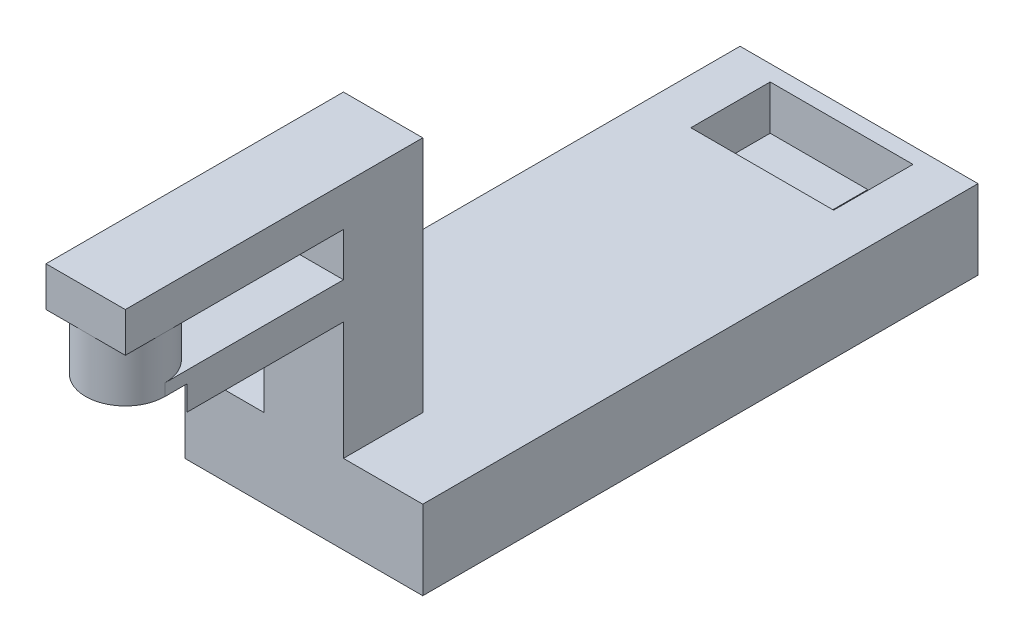
SolidWorks part; units mm, degrees
ref_plane "Front Plane" through (0, 0, 0) normal (0, 0, 1) x (1, 0, 0)
ref_plane "Top Plane" through (0, 0, 0) normal (0, 1, 0) x (1, 0, 0)
ref_plane "Right Plane" through (0, 0, 0) normal (1, 0, 0) x (0, 0, -1)
sketch "Sketch1" plane through (0, 0, 0) normal (0, 0, 1) x (1, 0, 0)
  line L1 (-6.35, -25.4) -> (6.35, -25.4)
  line L2 (-6.35, -25.4) -> (-6.35, 25.4)
  line L3 (-6.35, 25.4) -> (6.35, 25.4)
  line L4 (6.35, -25.4) -> (6.35, 25.4)
  line L5 (-6.35, -25.4) -> (6.35, 25.4) construction
  line L6 (-6.35, 25.4) -> (6.35, -25.4) construction
  point P0 (0, 0)
  dimension "D1" = 12.7
  dimension "D2" = 50.8
extrude "Boss-Extrude1" add sketch "Sketch1" along normal blind 12.7
sketch "Sketch2" plane through (0, 0, 12.7) normal (0, 0, 1) x (1, 0, 0)
  line L0 (6.35, -25.4) -> (6.35, 25.4) construction
  line L1 (-6.35, 25.4) -> (6.35, 25.4)
  line L2 (-6.35, 25.4) -> (-6.35, 19.05)
  line L3 (-6.35, 19.05) -> (6.35, 19.05)
  line L4 (6.35, 25.4) -> (6.35, 19.05)
  line L5 (-6.35, 25.4) -> (-6.35, -25.4) construction
  line L6 (-6.35, 12.065) -> (6.35, 12.065)
  line L7 (-6.35, 12.065) -> (-6.35, 6.223)
  line L8 (-6.35, 6.223) -> (6.35, 6.223)
  line L9 (6.35, 12.065) -> (6.35, 6.223)
  dimension "D1" = 6.35
  dimension "D2" = 6.985
  dimension "D3" = 5.842
extrude "Boss-Extrude2" add sketch "Sketch2" along normal blind 34.925
sketch "Sketch4" plane through (0, 12.065, 0) normal (0, 1, 0) x (1, 0, 0)
  line L0 (6.35, -47.625) -> (-6.35, -47.625) construction
  line L1 (0, -41.275) -> (-6.35, -41.275) construction
  line L3 (-6.35, -47.625) -> (-6.35, -12.7) construction
  line L5 (0, -41.275) -> (6.35, -41.275) construction
  line L6 (6.35, -47.625) -> (6.35, -12.7) construction
  circle A0 centre (0, -41.275) radius 6.35
  dimension "D1" = 12.7
extrude "Boss-Extrude3" add sketch "Sketch4" along normal up to surface (6.985 mm away) up to face at (0, 19.05, 30.1625)
sketch "Sketch5" plane through (0, 6.223, 0) normal (0, -1, 0) x (1, 0, 0)
  line L0 (3.8, 30.925) -> (3.8, 16.775) construction
  line L1 (-3.8, 16.775) -> (-3.8, 30.925) construction
  line L2 (3.8, 30.925) -> (3.8, 16.775)
  line L3 (-3.8, 16.775) -> (-3.8, 30.925)
  line L4 (6.35, 47.625) -> (3.4986, 47.625)
  line L5 (-6.35, 47.625) -> (6.35, 47.625) construction
  line L6 (6.35, 47.625) -> (6.35, 44.7736)
  line L7 (6.35, 47.625) -> (6.35, 12.7) construction
  line L8 (-6.35, 47.625) -> (-3.4986, 47.625)
  line L9 (-6.35, 47.625) -> (-6.35, 44.7736)
  line L10 (-6.35, 47.625) -> (-6.35, 12.7) construction
  line L11 (6.35, 44.7736) -> (6.35, 37.7764)
  line L12 (-6.35, 44.7736) -> (-6.35, 37.7764)
  line L13 (3.4986, 47.625) -> (-3.4986, 47.625)
  arc A0 (-2.75, 47.9832) -> (-6.8053, 43.775) centre (0, 41.275) ccw construction
  arc A1 (-3.8, 30.925) -> (-4.4708, 34.5259) centre (-13.8, 30.925) ccw construction
  arc A2 (3.972, 32.7719) -> (3.8, 30.925) centre (13.8, 30.925) ccw construction
  arc A3 (-3.8, 16.775) -> (3.8, 16.775) centre (0, 16.775) ccw construction
  arc A4 (5.8, 36.925) -> (6.35, 37.7764) centre (0, 41.275) ccw
  arc A5 (-3.8, 30.925) -> (-5.8, 36.925) centre (-13.8, 30.925) ccw
  arc A6 (5.8, 36.925) -> (3.8, 30.925) centre (13.8, 30.925) ccw
  arc A7 (-3.8, 16.775) -> (3.8, 16.775) centre (0, 16.775) ccw
  arc A9 (-6.35, 37.7764) -> (-5.8, 36.925) centre (0, 41.275) ccw
  arc A10 (6.35, 41.275) -> (0, 47.625) centre (0, 41.275) ccw construction
  arc A11 (0, 47.625) -> (-6.35, 41.275) centre (0, 41.275) ccw construction
  arc A12 (6.35, 41.275) -> (0, 47.625) centre (0, 41.275) ccw
  arc A13 (0, 47.625) -> (-6.35, 41.275) centre (0, 41.275) ccw
  line M2 (6.35, 12.7) -> (6.35, 47.625)
  line M3 (6.35, 47.625) -> (-6.35, 47.625)
  line M4 (-6.35, 47.625) -> (-6.35, 12.7)
extrude "Cut-Extrude1" cut sketch "Sketch5" against normal up to surface (3.937 mm away) contours A12 A13 L12 A9 A5 L3 A7 L2 A6 A4 M2 | A13 L13 M3 M4 | A12 L11 M2 M3 region at (0, 6.223, 32.0131) region at (4.9316, 6.223, 46.2066) region at (-4.9316, 6.223, 46.2066)
extrude "Cut-Extrude2" cut sketch "Sketch5<3>" against normal up to surface (12.827 mm away) contours A13 L13 M3 M4 | A12 L11 M2 M3 region at (4.9316, 6.223, 46.2066) region at (-4.9316, 6.223, 46.2066) up to face at (0, 19.05, 25.4)
sketch "Sketch5<3>" plane through (0, 6.223, 0) normal (0, -1, 0) x (1, 0, 0) same geometry as "Sketch5"
sketch "Sketch6" plane through (0, 0, 0) normal (0, 0, -1) x (-1, 0, 0)
  line L1 (-19.05, -25.4) -> (19.05, -25.4)
  line L2 (-19.05, -25.4) -> (-19.05, -12.7)
  line L3 (-19.05, -12.7) -> (19.05, -12.7)
  line L4 (19.05, -25.4) -> (19.05, -12.7)
  line L5 (-19.05, -25.4) -> (19.05, -12.7) construction
  line L6 (-19.05, -12.7) -> (19.05, -25.4) construction
  point P0 (0, -19.05)
  dimension "D1" = 12.7
  dimension "D2" = 38.1
extrude "Boss-Extrude4" add sketch "Sketch6" along normal blind 88.9 from surface starting at face at (0, -9.5885, 12.7)
sketch "Sketch7" plane through (0, -12.7, 0) normal (0, 1, 0) x (1, 0, 0)
  line L0 (19.05, 76.2) -> (19.05, -12.7) construction
  line L1 (-11.684, 73.66) -> (11.176, 73.66)
  line L2 (-11.684, 73.66) -> (-11.684, 60.96)
  line L3 (-11.684, 60.96) -> (11.176, 60.96)
  line L4 (11.176, 73.66) -> (11.176, 60.96)
  line L6 (-19.05, 76.2) -> (19.05, 76.2) construction
  dimension "D1" = 22.86
  dimension "D2" = 12.7
  dimension "D3" = 2.54
  dimension "D4" = 7.874
extrude "Cut-Extrude3" cut sketch "Sketch7" against normal blind 7.112
sketch "Sketch9" plane through (0, -19.812, 0) normal (0, 1, 0) x (1, 0, 0)
  line L0 (11.176, 73.66) -> (-11.684, 73.66) construction
  line L1 (3.937, 73.66) -> (6.731, 73.66)
  line L2 (3.937, 73.66) -> (3.937, 60.96)
  line L3 (3.937, 60.96) -> (6.731, 60.96)
  line L4 (6.731, 73.66) -> (6.731, 60.96)
  line L5 (-11.684, 60.96) -> (11.176, 60.96) construction
  line L6 (-11.684, 73.66) -> (-11.684, 60.96) construction
  dimension "D1" = 2.794
  dimension "D2" = 15.621
extrude "Cut-Extrude4" cut sketch "Sketch9" against normal through all
